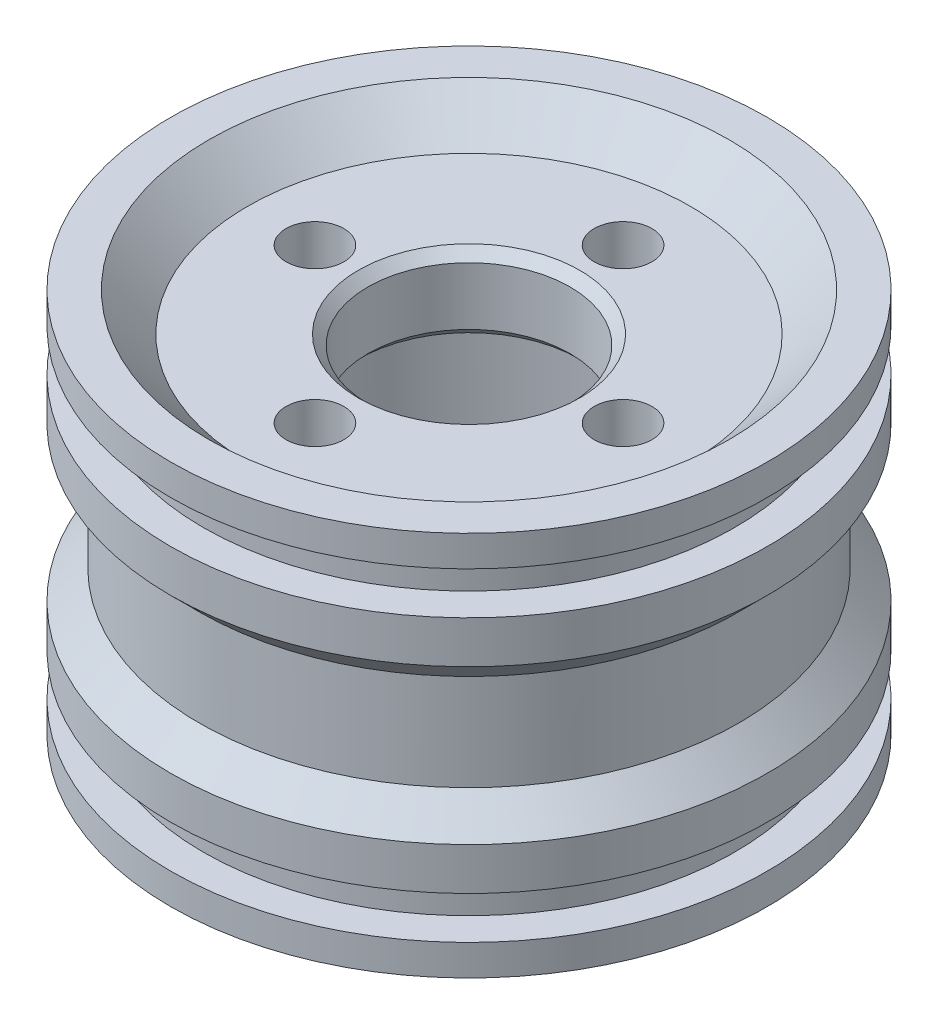
SolidWorks part; units mm, degrees
ref_plane "前视基准面" through (0, 0, 0) normal (0, 0, 1) x (1, 0, 0)
ref_plane "上视基准面" through (0, 0, 0) normal (0, 1, 0) x (1, 0, 0)
ref_plane "右视基准面" through (0, 0, 0) normal (1, 0, 0) x (0, 0, -1)
other "Configuration Table"
sketch "草图1" plane through (0, 0, 0) normal (0, 1, 0) x (1, 0, 0)
  circle A0 centre (0, 0) radius 15.5
  dimension "D1" = 31
extrude "凸台-拉伸1" add sketch "草图1" along normal mid plane 20
sketch "草图2" plane through (0, 0, 0) normal (0, 0, 1) x (1, 0, 0)
  line L0 (15.5, -10) -> (15.5, 10) construction
  line L1 (15.5, 8.4) -> (0, 8.4) construction
  line L2 (15.5, 8.4) -> (15.5, 6.2) construction
  line L3 (15.5, 6.2) -> (0, 6.2) construction
  line L4 (0, 8.4) -> (0, 6.2) construction
  line L5 (15.5, 10) -> (-15.5, 10) construction
  line L7 (15.5, 8.4) -> (13.8, 8.4)
  line L8 (15.5, 8.4) -> (15.5, 6.2)
  line L9 (15.5, 6.2) -> (13.8, 6.2)
  line L10 (13.8, 8.4) -> (13.8, 6.2)
  dimension "D1" = 2.2
  dimension "D2" = 1.6
  dimension "D3" = 1.7
revolve "切除-旋转1" cut sketch "草图2" angle 360 about L4
mirror "镜向1" about plane through (0, 0, 0) normal (0, 1, 0) of "切除-旋转1"
sketch "草图4" plane through (0, -10, 0) normal (0, -1, 0) x (1, 0, 0)
  circle A0 centre (0, 0) radius 11.5
  dimension "D1" = 23
extrude "切除-拉伸1" cut sketch "草图4" against normal blind 14
sketch "草图5" plane through (0, 10, 0) normal (0, 1, 0) x (1, 0, 0)
  circle A0 centre (0, 0) radius 5.25
  dimension "D1" = 10.5
extrude "切除-拉伸2" cut sketch "草图5" against normal blind 15 contours A0 region at (0, 10, 0)
chamfer "倒角1" distance 2 angle 45 1 edges at (0, -10, -11.5)
sketch "草图6" plane through (0, 10, 0) normal (0, 1, 0) x (1, 0, 0)
  circle A0 centre (0, 0) radius 5
  circle A1 centre (0, 0) radius 11.5
  dimension "D1" = 23
  dimension "D2" = 10
extrude "切除-拉伸3" cut sketch "草图6" against normal blind 2
chamfer "倒角2" distance 2 angle 45 1 edges at (0, 10, 11.5)
ref_axis "基准轴1" through (0, 4, 0) along (0, 1, 0)
sketch "草图7" plane through (0, 0, 0) normal (1, 0, 0) x (0, 0, -1)
  line L0 (15.5, -6.2) -> (15.5, 6.2) construction
  line L1 (14, -4) -> (15.5, -4)
  line L2 (14, -4) -> (14, 4)
  line L3 (14, 4) -> (15.5, 4)
  line L4 (15.5, -4) -> (15.5, 4)
  line L5 (14, -4) -> (15.5, 4) construction
  line L6 (14, 4) -> (15.5, -4) construction
  point P0 (14.75, 0)
  dimension "D1" = 1.5
  dimension "D2" = 8
sketch "草图8" plane through (0, 4, 0) normal (0, -1, 0) x (1, 0, 0)
  circle A0 centre (-8, 0) radius 1.5
  point P2 (0, 0)
  dimension "D1" = 3
  dimension "D2" = 8
extrude "切除-拉伸4" cut sketch "草图8" against normal blind 10
pattern_circular "阵列(圆周)1" count 4 over 360 about axis through (0, 4, 0) along (0, 1, 0) of "切除-拉伸4"
revolve "切除-旋转2" cut sketch "草图7" angle 360 about axis through (0, 4, 0) along (0, 1, 0)
chamfer "倒角5" distance 1.5 angle 45 2 edges at (0, 4, -14) (0, -4, -14)
chamfer "倒角4" distance 0.5 angle 45 3 edges at (0, 4, -11.5) (0, 8, 5.25) (0, 4, -5.25)
sketch "草图9" plane through (0, 0, 0) normal (0, 0, 1) x (1, 0, 0)
  line L0 (15.5, 10) -> (-15.5, 10) construction
  circle A0 centre (0, 3) radius 1.5
  point P4 (0, 0)
  dimension "D2" = 3
  dimension "D1" = 7
